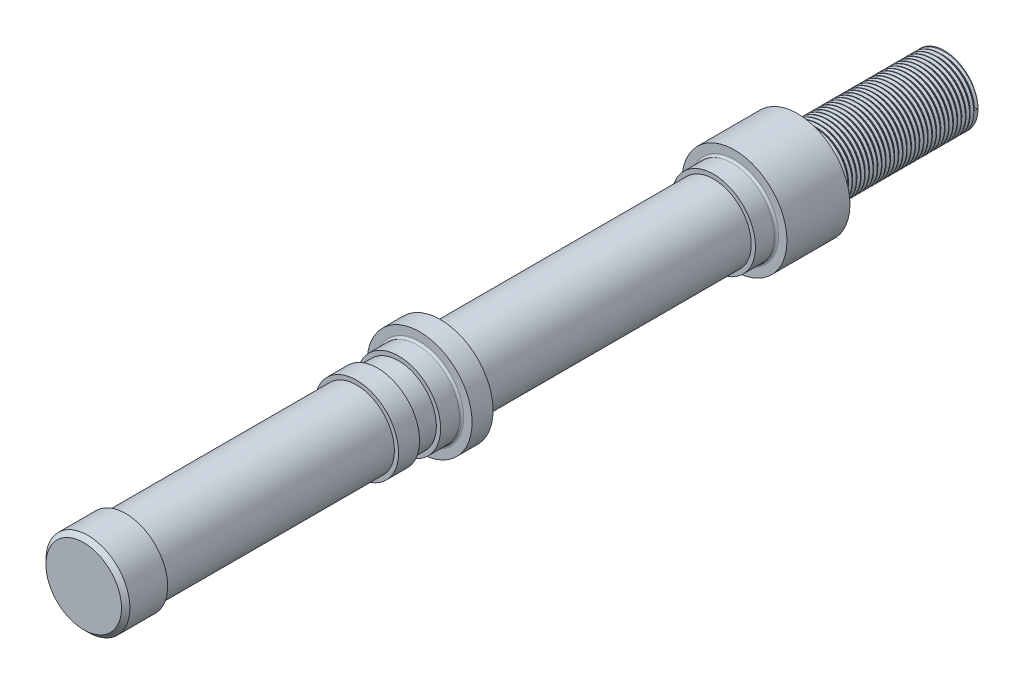
SolidWorks part; units mm, degrees
ref_plane "正面" through (0, 0, 0) normal (0, 0, 1) x (1, 0, 0)
ref_plane "平面" through (0, 0, 0) normal (0, 1, 0) x (1, 0, 0)
ref_plane "右側面" through (0, 0, 0) normal (1, 0, 0) x (0, 0, -1)
sketch "ｽｹｯﾁ1" plane through (0, 0, 0) normal (0, 0, 1) x (1, 0, 0)
  circle A0 centre (0, 0) radius 8
  dimension "D1" = 16
extrude "ﾎﾞｽ - 押し出し1" add sketch "ｽｹｯﾁ1" along normal blind 35
sketch "ｽｹｯﾁ2" plane through (0, 0, 35) normal (0, 0, 1) x (1, 0, 0)
  circle A0 centre (0, 0) radius 12.5
  dimension "D1" = 25
extrude "ﾎﾞｽ - 押し出し2" add sketch "ｽｹｯﾁ2" along normal blind 15
sketch "ｽｹｯﾁ3" plane through (0, 0, 50) normal (0, 0, 1) x (1, 0, 0)
  circle A0 centre (0, 0) radius 10
  dimension "D1" = 20
extrude "ﾎﾞｽ - 押し出し3" add sketch "ｽｹｯﾁ3" along normal blind 5
sketch "ｽｹｯﾁ4" plane through (0, 0, 55) normal (0, 0, 1) x (1, 0, 0)
  circle A0 centre (0, 0) radius 9
  dimension "D1" = 18
extrude "ﾎﾞｽ - 押し出し4" add sketch "ｽｹｯﾁ4" along normal blind 65
sketch "ｽｹｯﾁ5" plane through (0, 0, 120) normal (0, 0, 1) x (1, 0, 0)
  circle A0 centre (0, 0) radius 12.5
  dimension "D1" = 25
extrude "ﾎﾞｽ - 押し出し5" add sketch "ｽｹｯﾁ5" along normal blind 5
sketch "ｽｹｯﾁ6" plane through (0, 0, 125) normal (0, 0, 1) x (1, 0, 0)
  circle A0 centre (0, 0) radius 10
  dimension "D1" = 20
extrude "ﾎﾞｽ - 押し出し6" add sketch "ｽｹｯﾁ6" along normal blind 5
sketch "ｽｹｯﾁ7" plane through (0, 0, 130) normal (0, 0, 1) x (1, 0, 0)
  circle A0 centre (0, 0) radius 9
  dimension "D1" = 18
extrude "ﾎﾞｽ - 押し出し7" add sketch "ｽｹｯﾁ7" along normal blind 5
sketch "ｽｹｯﾁ8" plane through (0, 0, 135) normal (0, 0, 1) x (1, 0, 0)
  circle A0 centre (0, 0) radius 10
  dimension "D1" = 20
extrude "ﾎﾞｽ - 押し出し8" add sketch "ｽｹｯﾁ8" along normal blind 5
sketch "ｽｹｯﾁ9" plane through (0, 0, 140) normal (0, 0, 1) x (1, 0, 0)
  circle A0 centre (0, 0) radius 9
  dimension "D1" = 18
extrude "ﾎﾞｽ - 押し出し9" add sketch "ｽｹｯﾁ9" along normal blind 55
sketch "ｽｹｯﾁ10" plane through (0, 0, 195) normal (0, 0, 1) x (1, 0, 0)
  circle A0 centre (0, 0) radius 10
  dimension "D1" = 20
extrude "ﾎﾞｽ - 押し出し10" add sketch "ｽｹｯﾁ10" along normal blind 10
thread "ねじ山1" pitch 1 profile "ねじ山の輪郭1" start angle 0, offset 0, length 0, pitch 1, diameter 16
ref_plane "平面2" through (8, 0, 0) normal (0, -1, 0) x (1, 0, 0)
sketch "ねじ山の輪郭1" plane through (8, 0, 0) normal (0, -1, 0) x (1, 0, 0)
  line L0 (0, 0) -> (0, 1) construction
  line L11 (0, 0) -> (0, 0.875)
  line L12 (0, 0.875) -> (-0.5413, 0.5625)
  line L13 (-0.5413, 0.5625) -> (-0.5413, 0.3125)
  line L15 (-0.5413, 0.3125) -> (0, 0)
  line L17 (-0.5413, 0.4375) -> (0, 0.4375) construction
  point P2 (0, 0)
  dimension "Pitch" = 1
  dimension "Profile_Angle" = 60
  dimension "Profile_Land" = 0.25
  dimension "Profile_Height" = 0.5413
chamfer "面取り1" distance 1 angle 45 1 edges at (10, 0, 205)
fillet "ﾌｨﾚｯﾄ1" radius 0.5 1 edges at (10, 0, 125)
fillet "ﾌｨﾚｯﾄ2" radius 0.5 1 edges at (10, 0, 50)
